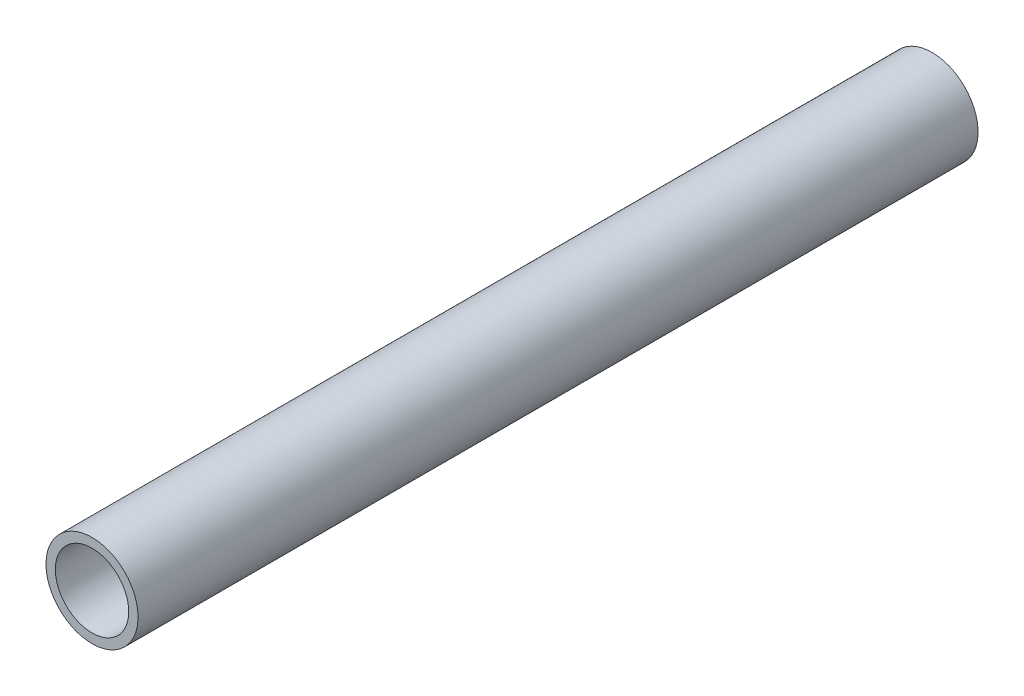
SolidWorks part; units mm, degrees
ref_plane "Front Plane" through (0, 0, 0) normal (0, 0, 1) x (1, 0, 0)
ref_plane "Top Plane" through (0, 0, 0) normal (0, 1, 0) x (1, 0, 0)
ref_plane "Right Plane" through (0, 0, 0) normal (1, 0, 0) x (0, 0, -1)
sketch "Sketch1" plane through (0, 0, 0) normal (0, 0, 1) x (1, 0, 0)
  line L0 (13.3223, 0) -> (16.7005, 0) construction
  circle A0 centre (0, 0) radius 16.7005
  circle A1 centre (0, 0) radius 13.3223
  dimension "OD" = 33.401
  dimension "ID" = 26.6446
  dimension "Wall Thickness" = 3.3782
sketch "Sketch2" plane through (0, 0, 0) normal (0, 0, 1) x (1, 0, 0)
  circle A1 centre (0, 0) radius 13.3223
  circle A3 centre (0, 0) radius 13.3223
  circle A5 centre (0, 0) radius 16.7005
  circle A6 centre (0, 0) radius 16.7005
  dimension "D1" = 0
  dimension "D2" = 0
extrude "Pipe Extrude" add sketch "Sketch2" along normal mid plane 304.8
ref_axis "Center Axis 1" through (-670.56, 0, 0) along (1, 0, 0)
ref_axis "Center Axis 2" through (0, 18.3845, 0) along (0, -1, 0)
ref_plane "Plane1" through (0, 0, -152.4) normal (0, 0, -1) x (-1, 0, 0)
ref_plane "Plane2" through (0, 0, 152.4) normal (0, 0, 1) x (1, 0, 0)
